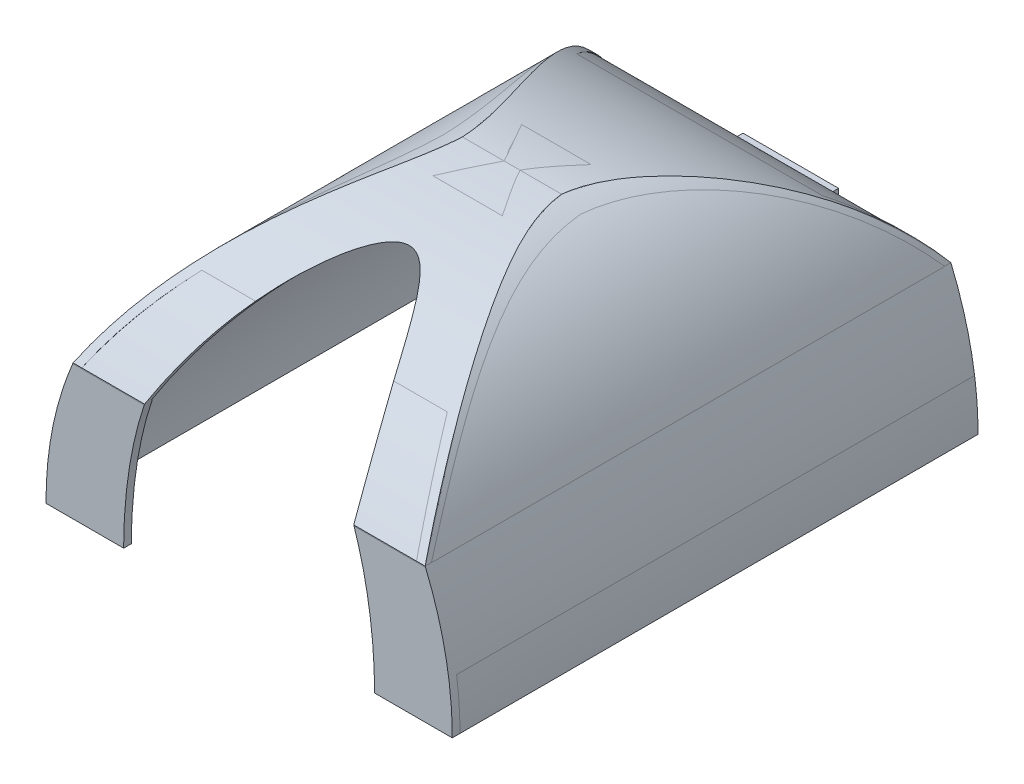
SolidWorks part; units mm, degrees
ref_plane "Front Plane" through (0, 0, 0) normal (0, 0, 1) x (1, 0, 0)
ref_plane "Top Plane" through (0, 0, 0) normal (0, 1, 0) x (1, 0, 0)
ref_plane "Right Plane" through (0, 0, 0) normal (1, 0, 0) x (0, 0, -1)
sketch "Sketch1" plane through (0, 0, 0) normal (0, 0, 1) x (1, 0, 0)
  line L0 (-191.1086, 0) -> (191.1086, 0) construction
  line L1 (-63.75, 0) -> (63.75, 0)
  ellipse E0 centre (0, 0) end of major axis (0, 85) minor radius 63.75
  ellipse E1 centre (0, 0) end of major axis (0, 82.5) minor radius 61.25
  point P4 (0, 0)
  dimension "D1" = 85
  dimension "D2" = 2.5
  dimension "D3" = 2.5
  dimension "D4" = 122.5
extrude "Boss-Extrude1" add sketch "Sketch1" along normal blind 165 contours E1 L1 E0 region at (-46.8283, 54.9293, 0)
sketch "Sketch4" plane through (0, 0, 0) normal (0, 0, 1) x (1, 0, 0)
  line L0 (31.2524, -11.387) -> (46.2524, -11.387) construction
  line L1 (-63.75, 0) -> (63.5055, 0)
  line L2 (-63.75, 0) -> (-63.75, 84.8599)
  line L3 (-63.75, 84.8599) -> (63.5055, 84.8599)
  line L4 (63.5055, 0) -> (63.5055, 84.8599)
  line L7 (0, -104.4515) -> (0, 104.4515) construction
  line L8 (-31.2524, -11.387) -> (-46.2524, -11.387) construction
  line L9 (-31.2524, 5) -> (-46.2524, 5)
  line L10 (-31.2524, -27.774) -> (-46.2524, -27.774)
  line L11 (31.2524, 5) -> (46.2524, 5)
  line L12 (31.2524, -27.774) -> (46.2524, -27.774)
  arc A2 (-31.2524, 5) -> (-31.2524, -27.774) centre (-31.2524, -11.387) cw
  arc A3 (-46.2524, -27.774) -> (-46.2524, 5) centre (-46.2524, -11.387) cw
  arc A4 (31.2524, 5) -> (31.2524, -27.774) centre (31.2524, -11.387) ccw
  arc A5 (46.2524, -27.774) -> (46.2524, 5) centre (46.2524, -11.387) ccw
  spline S0 degree 1 poles (-63.75, 0) (-63.75, 9.5118) knots 0 0 1 1
  point P8 (38.7524, -11.387)
  point P18 (0, 0)
  point P20 (-38.7524, -11.387)
  dimension "D2" = 15
  dimension "D1" = 5
extrude "Boss-Extrude3" add sketch "Sketch4" along normal blind 2 contours L1 A3 L9 A2 L4 L3 L2 region at (-0.1259, 43.6278, 0)
sketch "Sketch5" plane through (0, 0, 0) normal (0, 0, 1) x (1, 0, 0)
  line L1 (-65.159, 87.3395) -> (65.5718, 87.3395)
  line L2 (-65.159, 87.3395) -> (-65.159, 0)
  line L3 (-65.159, 0) -> (65.5718, 0)
  line L4 (65.5718, 87.3395) -> (65.5718, 0)
  ellipse E0 centre (0, 0) end of major axis (0, 85) minor radius 63.75
extrude "Cut-Extrude2" cut sketch "Sketch5" against normal through all both and the other way through all contours E0 L3 L4 L1 L2 region at (0.2064, 85.7673, 0)
sketch "Sketch7" plane through (0, 0, 0) normal (0, 0, 1) x (1, 0, 0)
  line L1 (-15, 0) -> (15, 0)
  line L2 (-15, 0) -> (-15, 40)
  line L3 (-15, 40) -> (15, 40)
  line L4 (15, 0) -> (15, 40)
  dimension "D1" = 30
  dimension "D2" = 15
  dimension "D3" = 40
extrude "Boss-Extrude4" add sketch "Sketch7" along normal blind 10 from offset 5 offset against normal yes
sketch "Sketch8" plane through (0, 0, 0) normal (0, 0, 1) x (1, 0, 0)
  line L0 (-15, 0) -> (15, 0) construction
  line L1 (12, 0) -> (-12, 0)
  line L2 (12, 0) -> (12, 37)
  line L3 (12, 37) -> (-12, 37)
  line L4 (-12, 0) -> (-12, 37)
  line L5 (15, 40) -> (15, 0) construction
  line L6 (-15, 40) -> (-15, 0) construction
  line L7 (-15, 40) -> (15, 40) construction
  dimension "D1" = 3
  dimension "D2" = 3
  dimension "D3" = 3
extrude "Cut-Extrude3" cut sketch "Sketch8" against normal through all both and the other way through all
sketch "Sketch13" plane through (0, 0, 0) normal (1, 0, 0) x (0, 0, -1)
  line L0 (-82.5, 188.0425) -> (-82.5, -18.0425) construction
  line L1 (0, 42.43) -> (0, 40)
  line L2 (0, 0) -> (0, 84.8599) construction
  line L7 (117.3704, 0) -> (-239.4861, 0) construction
  line L8 (-165, 42.43) -> (-165, 40)
  spline S0 degree 2 poles (0, 40) (-30.5489, 78.3669) (-82.5, 80) knots 0 0 0 1 1 1
  spline S1 degree 2 poles (-165, 40) (-134.4511, 78.3669) (-82.5, 80) knots 0 0 0 1 1 1
  spline S2 degree 2 poles (0, 42.43) (-31.5656, 80.5446) (-82.5, 82.43) knots 0 0 0 1 1 1
  spline S3 degree 2 poles (-165, 42.43) (-133.4344, 80.5446) (-82.5, 82.43) knots 0 0 0 1 1 1
  point P3 (-82.5, 85)
  point P21 (-61.0579, 0)
  dimension "D2" = 80
extrude "Boss-Extrude5" add sketch "Sketch13" against normal blind 140 from offset 70
sketch "Sketch15" plane through (0, 0, 0) normal (1, 0, 0) x (0, 0, -1)
  line L0 (-82.5, 183.8663) -> (-82.5, -19.0063) construction
  line L1 (0, 42.43) -> (0, 100.7289)
  line L2 (0, 100.7289) -> (-165, 100.7289)
  line L3 (-165, 100.7289) -> (-165, 42.43)
  parabola Q0 (0, 42.43) -> (-82.5, 82.43) focus (-56.8904, 24.6112) apex (-32.8096, 69.6541) construction
  parabola Q1 (0, 42.43) -> (-82.5, 82.43) focus (-56.8904, 24.6112) apex (-32.8096, 69.6541) construction
  parabola Q2 (0, 42.43) -> (-82.5, 82.43) focus (-56.8904, 24.6112) apex (-32.8096, 69.6541) construction
  parabola Q3 (0, 42.43) -> (-82.5, 82.43) focus (-56.8904, 24.6112) apex (-32.8096, 69.6541) construction
  parabola Q4 (0, 42.43) -> (-82.5, 82.43) focus (-56.8904, 24.6112) apex (-32.8096, 69.6541) construction
  spline S0 degree 3 poles (0, 42.43) (-19.3644, 67.4289) (-51.2439, 81.6009) (-82.5, 82.43) knots 0 0 0 0 1 1 1 1
  spline S1 degree 3 poles (-165, 42.43) (-145.6356, 67.4289) (-113.7561, 81.6009) (-82.5, 82.43) knots 0 0 0 0 1 1 1 1
  point P32 (-82.5, 82.43)
extrude "Cut-Extrude9" cut sketch "Sketch15" against normal through all both and the other way through all
sketch "Sketch16" plane through (0, 0, 0) normal (0, 0, 1) x (1, 0, 0)
  line L0 (-63.75, 0) -> (-90.3828, 0)
  line L1 (-90.3828, 0) -> (-90.3828, 92.2084)
  line L2 (-90.3828, 92.2084) -> (83.7396, 92.2084)
  line L3 (83.7396, 92.2084) -> (83.7396, 0)
  line L4 (83.7396, 0) -> (63.75, 0)
  ellipse E0 centre (0, 0) end of major axis (0, 85.0059) minor radius 63.75
extrude "Cut-Extrude10" cut sketch "Sketch16" against normal through all both and the other way through all contours E0 L4 L3 L2 L1 L0 region at (-77.0664, 1.9703, 0)
sketch "Sketch17" plane through (0, 0, 0) normal (0, 0, 1) x (1, 0, 0)
  line L0 (0, -91.7444) -> (0, 91.7444) construction
  line L2 (-15, 0) -> (15, 0)
  line L3 (-15, 0) -> (-15, 70)
  line L4 (-15, 70) -> (15, 70)
  line L5 (15, 0) -> (15, 70)
  point P4 (0, 0)
  dimension "D1" = 70
  dimension "D2" = 30
  dimension "D3" = 15
extrude "Cut-Extrude11" cut sketch "Sketch17" along normal blind 140 from offset 100
sketch "Sketch18" plane through (0, 0, 0) normal (1, 0, 0) x (0, 0, -1)
  line L0 (-165, 0) -> (0, 0) construction
  line L1 (-165, 42.43) -> (-162.57, 42.43)
  line L2 (-165, 42.43) -> (-165, 0)
  line L3 (-165, 0) -> (-162.57, 0)
  line L4 (-162.57, 42.43) -> (-162.57, 0)
  dimension "D1" = 2.43
extrude "Boss-Extrude6" add sketch "Sketch18" along normal blind 140 from offset 70 offset against normal yes
sketch "Sketch19" plane through (0, 0, 0) normal (0, 0, 1) x (1, 0, 0)
  line L1 (-15, 70) -> (15, 70)
  line L2 (-15, 70) -> (-15, 0)
  line L3 (-15, 0) -> (15, 0)
  line L4 (15, 70) -> (15, 0)
extrude "Cut-Extrude12" cut sketch "Sketch19" along normal blind 140 from offset 100
sketch "Sketch20" plane through (0, 0, 0) normal (0, 0, 1) x (1, 0, 0)
  line L0 (55.2401, 42.43) -> (74.4206, 42.43)
  line L1 (74.4206, 42.43) -> (74.4206, 0)
  line L2 (74.4206, 0) -> (63.75, 0)
  line L3 (-63.75, 0) -> (-76.0845, 0)
  line L4 (-76.0845, 0) -> (-76.0845, 44.492)
  line L5 (-76.0845, 44.492) -> (-55.2401, 42.43)
  ellipse E0 centre (0, 0) end of major axis (0, 85) minor radius 63.75 (63.5055, 7.4378) -> (56.25, 39.9999) ccw construction
  ellipse E1 centre (0, 0) end of major axis (0, 85) minor radius 63.75 (-56.25, 39.9999) -> (-63.75, 0) ccw construction
  spline S0 degree 2 poles (63.75, 0) (63.7889, 21.9478) (55.2401, 42.43) knots 0 0 0 1 1 1
  spline S1 degree 2 poles (-55.2401, 42.43) (-63.8127, 22.2509) (-63.75, 0) knots 0 0 0 1 1 1
extrude "Cut-Extrude13" cut sketch "Sketch20" along normal through all both and the other way through all
sketch "Sketch22" plane through (0, 0, 0) normal (0, 0, 1) x (1, 0, 0)
  line L0 (0, -89.705) -> (0, 89.705) construction
  line L1 (63.75, 0) -> (15, 0) construction
  ellipse E0 centre (0, 0) end of major axis (0, 76.839) minor radius 39.375
  point P4 (0, 0)
extrude "Cut-Extrude18" cut sketch "Sketch22" along normal blind 140 from offset 80
